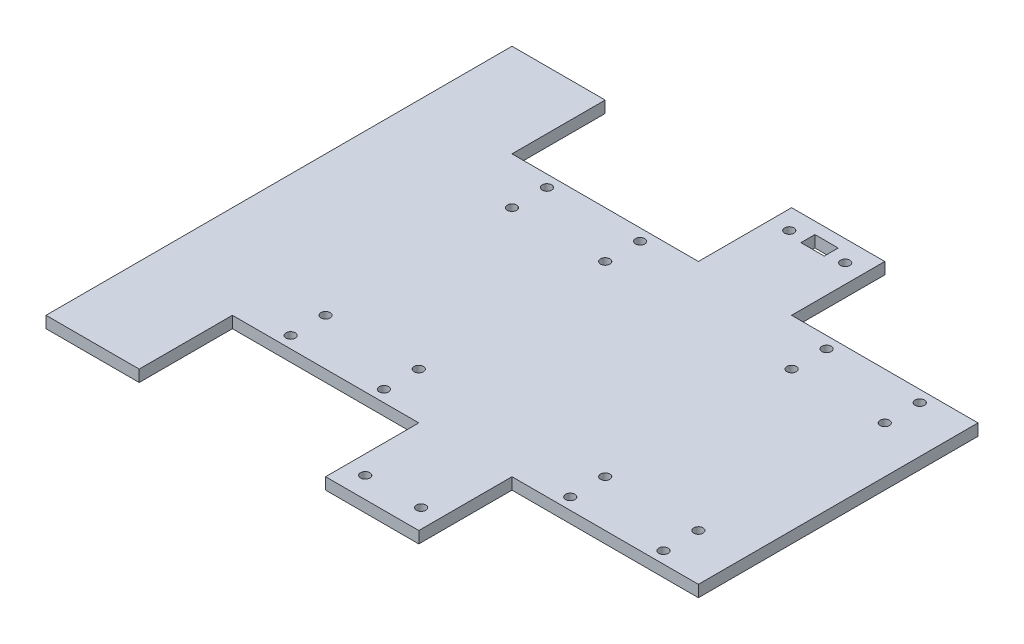
SolidWorks part; units mm, degrees
ref_plane "Front Plane" through (0, 0, 0) normal (0, 0, 1) x (1, 0, 0)
ref_plane "Top Plane" through (0, 0, 0) normal (0, 1, 0) x (1, 0, 0)
ref_plane "Right Plane" through (0, 0, 0) normal (1, 0, 0) x (0, 0, -1)
sketch "Sketch1" plane through (0, 0, 0) normal (0, 1, 0) x (1, 0, 0)
  line L0 (0, 0) -> (0, 152.4) construction
  line L13 (0, 152.4) -> (101.6, 152.4)
  line L16 (152.4, 152.4) -> (254, 152.4)
  line L17 (254, 152.4) -> (254, 0)
  line L18 (254, 0) -> (152.4, 0)
  line L21 (101.6, 0) -> (0, 0)
  line L22 (101.6, 152.4) -> (101.6, 203.2)
  line L23 (101.6, 203.2) -> (152.4, 203.2)
  line L24 (152.4, 203.2) -> (152.4, 152.4)
  line L25 (101.6, 0) -> (101.6, -50.8)
  line L26 (101.6, -50.8) -> (152.4, -50.8)
  line L27 (152.4, -50.8) -> (152.4, 0)
  line L28 (0, 152.4) -> (0, 203.2)
  line L29 (0, 203.2) -> (-50.8, 203.2)
  line L30 (-50.8, 203.2) -> (-50.8, -50.8)
  line L31 (-50.8, -50.8) -> (0, -50.8)
  line L32 (0, -50.8) -> (0, 0)
  dimension "D1" = 254
  dimension "D2" = 152.4
  dimension "D3" = 101.6
  dimension "D4" = 50.8
  dimension "D5" = 50.8
  dimension "D6" = 50.8
  dimension "D7" = 50.8
extrude "Boss-Extrude1" add sketch "Sketch1" along normal blind 6.35
sketch "Sketch2" plane through (0, 6.35, 0) normal (0, 1, 0) x (1, 0, 0)
  line L0 (152.4, 203.2) -> (101.6, 203.2) construction
  line L1 (133.35, 189.23) -> (120.65, 189.23)
  line L2 (133.35, 189.23) -> (133.35, 196.85)
  line L3 (133.35, 196.85) -> (120.65, 196.85)
  line L4 (120.65, 189.23) -> (120.65, 196.85)
  point P6 (127, 203.2)
  dimension "D1" = 12.7
  dimension "D2" = 7.62
  dimension "D3" = 6.35
  dimension "D4" = 19.05
extrude "Cut-Extrude1" cut sketch "Sketch2" against normal through all contours L2 L3 L4 L1
sketch "Sketch3" plane through (0, 0, 0) normal (0, -1, 0) x (1, 0, 0)
  line L0 (0, -76.2) -> (254, -76.2) construction
  line L2 (254, 0) -> (254, -152.4) construction
  line L3 (254, -152.4) -> (152.4, -152.4) construction
  line L4 (101.6, 50.8) -> (152.4, 50.8) construction
  line L5 (127, 50.8) -> (127, -203.2) construction
  line L6 (152.4, -203.2) -> (101.6, -203.2) construction
  line L7 (0, 0) -> (0, -152.4) construction
  line L8 (50.8, 0) -> (50.8, -152.4) construction
  line L9 (0, 0) -> (101.6, 0) construction
  line L10 (101.6, -152.4) -> (0, -152.4) construction
  circle A0 centre (228.6, -146.05) radius 2.54
  circle A1 centre (177.8, -146.05) radius 2.54
  circle A2 centre (228.6, -127) radius 2.54
  circle A3 centre (177.8, -127) radius 2.54
  circle A4 centre (177.8, -25.4) radius 2.54
  circle A5 centre (228.6, -25.4) radius 2.54
  circle A6 centre (177.8, -6.35) radius 2.54
  circle A7 centre (228.6, -6.35) radius 2.54
  circle A8 centre (25.4, -6.35) radius 2.54
  circle A9 centre (76.2, -6.35) radius 2.54
  circle A10 centre (25.4, -25.4) radius 2.54
  circle A11 centre (76.2, -25.4) radius 2.54
  circle A12 centre (76.2, -127) radius 2.54
  circle A13 centre (25.4, -127) radius 2.54
  circle A14 centre (76.2, -146.05) radius 2.54
  circle A15 centre (25.4, -146.05) radius 2.54
  circle A16 centre (142.24, -191.77) radius 2.54
  circle A17 centre (111.76, -191.77) radius 2.54
  circle A18 centre (142.24, 39.37) radius 2.54
  circle A19 centre (111.76, 39.37) radius 2.54
  point P15 (0, -76.2)
  dimension "D1" = 5.08
  dimension "D4" = 5.08
  dimension "D6" = 15.24
  dimension "D2" = 50.8
  dimension "D3" = 25.4
  dimension "D5" = 6.35
  dimension "D7" = 19.05
  dimension "D8" = 11.43
extrude "Cut-Extrude2" cut sketch "Sketch3" against normal through all
